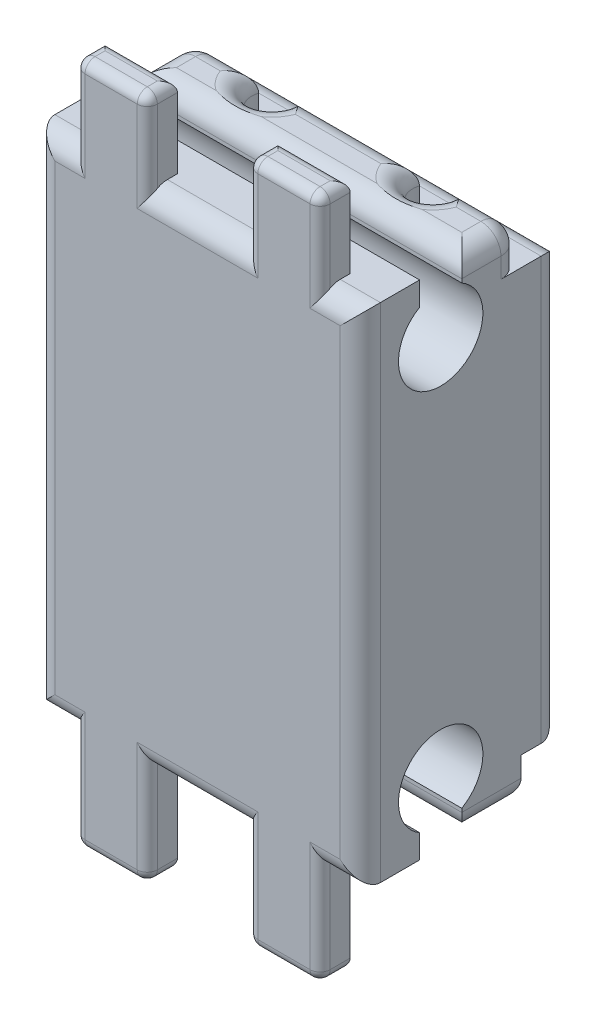
SolidWorks part; units mm, degrees
ref_plane "Front Plane" through (0, 0, 0) normal (0, 0, 1) x (1, 0, 0)
ref_plane "Top Plane" through (0, 0, 0) normal (0, 1, 0) x (1, 0, 0)
ref_plane "Right Plane" through (0, 0, 0) normal (1, 0, 0) x (0, 0, -1)
sketch "Sketch1" plane through (0, 0, 0) normal (0, 0, 1) x (1, 0, 0)
  line L0 (8.1, 0) -> (-8.1, 0)
  line L1 (0, 41.8397) -> (0, -28.0151) construction
  line L2 (-8.1, 0) -> (-8.1, 25)
  line L3 (-8.1, 25) -> (8.1, 25)
  line L4 (8.1, 25) -> (8.1, 0)
  point P6 (0, 0)
  dimension "D1" = 8.1
  dimension "D2" = 25
extrude "Boss-Extrude1" add sketch "Sketch1" along normal blind 10
sketch "Sketch11" plane through (0, 0, 0) normal (0, -1, 0) x (1, 0, 0)
  line L0 (-8.1, 10) -> (-8.1, 0) construction
  line L1 (-8.1, 0) -> (8.1, 0) construction
  line L4 (-8.1, 2.2959) -> (-8.1, 4.5918)
  line L5 (8.1, 2.2959) -> (-8.6978, 2.2959) construction
  line L6 (0, 0) -> (0, 6.168) construction
  circle A0 centre (4, 2.2959) radius 1
  circle A1 centre (-4, 2.2959) radius 1
  dimension "D2" = 2
  dimension "D1" = 4
  dimension "D3" = 2.2959
extrude "Cut-Extrude9" cut sketch "Sketch11" against normal up to surface (25 mm away) contours A0 | A1 region at (4, 0, 2.2959) region at (-4, 0, 2.2959) up to face at (0, 25, 5)
sketch "Sketch13" plane through (0, 0, 0) normal (0, 0, -1) x (-1, 0, 0)
  line L0 (-8.1, 0) -> (-8.1, 25) construction
  line L1 (-8.1, 2) -> (8.1, 2)
  line L3 (-8.1, 23) -> (8.1, 23)
  line L5 (8.1, 25) -> (8.1, 0) construction
  line L7 (-8.1, 25) -> (8.1, 25)
  line L8 (-8.1, 25) -> (-8.1, 23)
  line L9 (-8.1, 23) -> (8.1, 23)
  line L10 (8.1, 25) -> (8.1, 23)
  line L11 (-8.1, 2) -> (8.1, 2)
  line L12 (-8.1, 2) -> (-8.1, 0)
  line L13 (-8.1, 0) -> (8.1, 0)
  line L14 (8.1, 2) -> (8.1, 0)
  line M5 (8.1, 0) -> (8.1, 25)
  line M6 (8.1, 25) -> (-8.1, 25)
  line M7 (-8.1, 25) -> (-8.1, 0)
  line M8 (-8.1, 0) -> (8.1, 0)
  dimension "D1" = 2
  dimension "D2" = 2
extrude "Cut-Extrude10" cut sketch "Sketch13" against normal blind 2 contours L3 M7 M5 M6 | L1 M7 M8 M5 region at (0, 1, 0) region at (0, 24, 0)
ref_plane "Plane1" through (0, 0, 0) normal (-1, 0, 0) x (0, 0, 1)
sketch "Sketch14" plane through (0, 0, 0) normal (-1, 0, 0) x (0, 0, 1)
  line L0 (4.9501, 0) -> (7.0499, 0)
  line L1 (10, 0) -> (2, 0) construction
  line L2 (6, 3) -> (6, -1.5975) construction
  line L3 (4.9501, 0) -> (4.9501, 1.1813)
  line L4 (10, 25) -> (10, 0) construction
  line L5 (10, 12.5) -> (-2.9283, 12.5) construction
  line L8 (7.0499, 0) -> (7.0499, 1.1813)
  line L9 (4.9501, 25) -> (7.0499, 25)
  line L10 (7.0499, 25) -> (7.0499, 23.8187)
  line L11 (4.9501, 25) -> (4.9501, 23.8187)
  arc A0 (7.0499, 1.1813) -> (4.9501, 1.1813) centre (6, 3) ccw
  arc A1 (7.0499, 23.8187) -> (4.9501, 23.8187) centre (6, 22) cw
  point P10 (6, 0)
  dimension "D1" = 4.2
  dimension "D3" = 3
  dimension "D4" = 1.0499
extrude "Cut-Extrude16" cut sketch "Sketch14" against normal blind 14.1 and the other way blind 14.1 contours A0 | A0 | A1 | A1 region at (0, 2.6734, 6) region at (0, 22.3266, 6)
fillet "Fillet1" radius 1 26 edges at (8.1, 12.5, 10) (-8.1, 12.5, 10) (0, 25, 10) (0, 0, 10) (0, 2, 0) (-8.1, 24, 2) (8.1, 24, 2) (-8.1, 12.5, 0) (8.1, 12.5, 0) (0, 23, 0) (6.5276, 0, 2) (4, 0, 3.2959) (0, 0, 2) (-4, 0, 3.2959) (-6.5276, 0, 2) (-8.1, 0, 3.4751) (0, 0, 4.9501) (8.1, 0, 3.4751) (-8.1, 25, 3.4751) (-6.5276, 25, 2) (-4, 25, 3.2959) (0, 25, 2) (4, 25, 3.2959) (6.5276, 25, 2) (8.1, 25, 3.4751) (0, 25, 4.9501)
sketch "Sketch15" plane through (0, 0, 0) normal (0, -1, 0) x (1, 0, 0)
  line L0 (-7.1, 10) -> (7.1, 10) construction
  line L1 (-6.1, 10) -> (-2.5, 10)
  line L2 (-6.1, 10) -> (-6.1, 8.5)
  line L3 (-6.1, 8.5) -> (-2.5, 8.5)
  line L4 (-2.5, 10) -> (-2.5, 8.5)
  line L7 (2.5, 10) -> (6.1, 10)
  line L8 (2.5, 10) -> (2.5, 8.5)
  line L9 (2.5, 8.5) -> (6.1, 8.5)
  line L10 (6.1, 10) -> (6.1, 8.5)
  arc A0 (-7.1, 10) -> (-8.1, 9) centre (-7.1, 9) ccw construction
  dimension "D1" = 5
  dimension "D2" = 1
  dimension "D3" = 1
  dimension "D4" = 3.6
  dimension "D5" = 1.5
  dimension "D6" = 1.5
extrude "Boss-Extrude2" add sketch "Sketch15" along normal blind 5 and the other way blind 29
fillet "Fillet2" radius 0.5 24 edges at (4.3, -5, 10) (6.1, -5, 9.25) (4.3, -5, 8.5) (2.5, -5, 9.25) (-4.3, -5, 10) (-2.5, -5, 9.25) (-4.3, -5, 8.5) (-6.1, -5, 9.25) (-4.3, 29, 8.5) (-2.5, 29, 9.25) (-4.3, 29, 10) (-6.1, 29, 9.25) (4.3, 29, 8.5) (6.1, 29, 9.25) (4.3, 29, 10) (2.5, 29, 9.25) (6.1, -2, 10) (2.5, -2, 10) (-2.5, -2, 10) (-6.1, -2, 10) (-6.1, 26.5, 10) (-2.5, 26.5, 10) (2.5, 26.5, 10) (6.1, 26.5, 10)
